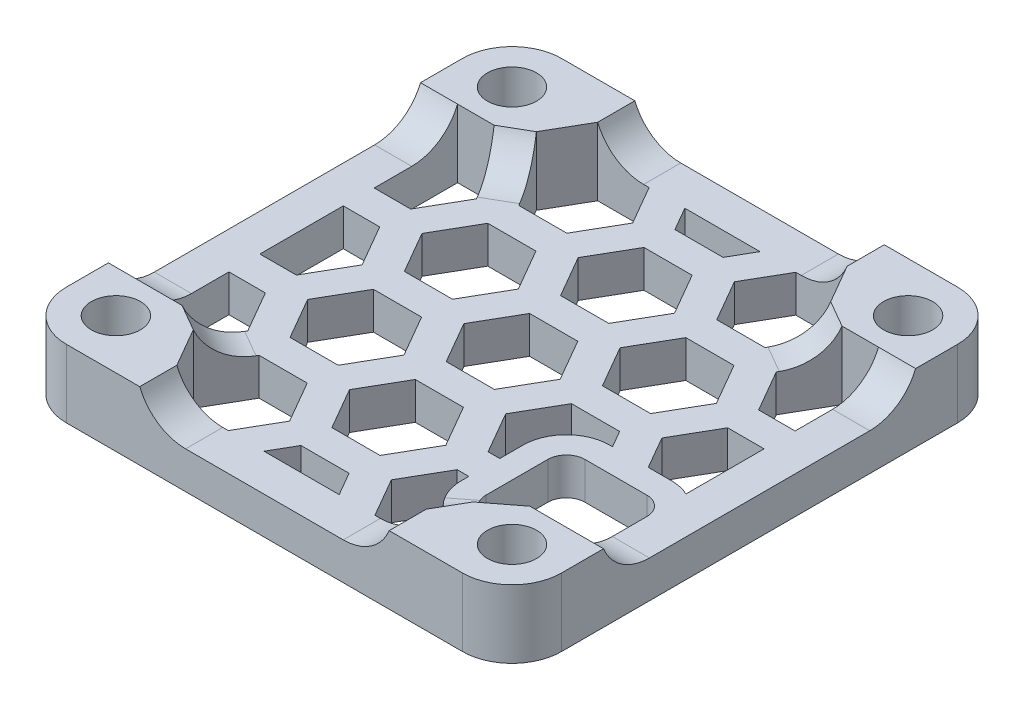
SolidWorks part; units mm, degrees
ref_plane "Front Plane" through (0, 0, 0) normal (0, 0, 1) x (1, 0, 0)
ref_plane "Top Plane" through (0, 0, 0) normal (0, 1, 0) x (1, 0, 0)
ref_plane "Right Plane" through (0, 0, 0) normal (1, 0, 0) x (0, 0, -1)
sketch "Sketch1" plane through (0, 0, 0) normal (0, 1, 0) x (1, 0, 0)
  line L1 (-16, -20) -> (16, -20)
  line L2 (-20, -16) -> (-20, 16)
  line L3 (-16, 20) -> (16, 20)
  line L4 (20, -16) -> (20, 16)
  line L5 (-18.8284, -18.8284) -> (16, 16) construction
  line L6 (-16, 16) -> (18.8284, -18.8284) construction
  circle A0 centre (-16, 16) radius 1.9844
  circle A1 centre (16, 16) radius 1.9844
  circle A2 centre (16, -16) radius 1.9844
  circle A3 centre (-16, -16) radius 1.9844
  arc A4 (-20, 16) -> (-16, 20) centre (-16, 16) cw
  arc A5 (16, 20) -> (20, 16) centre (16, 16) cw
  arc A6 (-16, -20) -> (-20, -16) centre (-16, -16) cw
  arc A7 (16, -20) -> (20, -16) centre (16, -16) ccw
  point P0 (0, 0)
  dimension "D2" = 3.9688
  dimension "D1" = 40
  dimension "D3" = 32
extrude "Boss-Extrude1" add sketch "Sketch1" along normal blind 3 contours L1 A7 L4 A5 L3 A4 L2 A6 A0 A1 A2 A3 | A0 | A1 | A2 | A3 region at (0, 0, 0) region at (-16, 0, -16) region at (16, 0, -16) region at (16, 0, 16) region at (-16, 0, 16)
sketch "Sketch2" plane through (0, 0, 0) normal (0, 1, 0) x (1, 0, 0)
  line L0 (5.0825, -2.9344) -> (2.9175, -1.6844) construction
  line L1 (1.945, -3.3688) -> (3.89, 0)
  line L2 (3.89, 0) -> (1.945, 3.3688)
  line L3 (1.945, 3.3688) -> (-1.945, 3.3688)
  line L4 (-1.945, 3.3688) -> (-3.89, 0)
  line L5 (-3.89, 0) -> (-1.945, -3.3688)
  line L6 (-1.945, -3.3688) -> (1.945, -3.3688)
  line L7 (9.945, -7.9876) -> (11.89, -4.6188)
  line L8 (11.89, -4.6188) -> (9.945, -1.25)
  line L9 (9.945, -1.25) -> (6.055, -1.25)
  line L10 (6.055, -1.25) -> (4.11, -4.6188)
  line L11 (4.11, -4.6188) -> (6.055, -7.9876)
  line L12 (6.055, -7.9876) -> (9.945, -7.9876)
  line L13 (2.9175, 1.6844) -> (5.0825, 2.9344) construction
  line L14 (9.945, 1.25) -> (11.89, 4.6188)
  line L15 (11.89, 4.6188) -> (9.945, 7.9876)
  line L16 (9.945, 7.9876) -> (6.055, 7.9876)
  line L17 (6.055, 7.9876) -> (4.11, 4.6188)
  line L18 (4.11, 4.6188) -> (6.055, 1.25)
  line L19 (6.055, 1.25) -> (9.945, 1.25)
  circle A0 centre (0, 0) radius 3.3688 construction
  circle A1 centre (8, -4.6188) radius 3.3688 construction
  circle A2 centre (8, 4.6188) radius 3.3688 construction
  dimension "D1" = 2.5
  dimension "D2" = 8
  dimension "D3" = 4.6188
sketch "Sketch3" plane through (0, 0, 0) normal (0, 1, 0) x (1, 0, 0)
  line L0 (6.055, -1.25) -> (4.11, -4.6188) construction
  line L1 (4.11, -4.6188) -> (6.055, -7.9876) construction
  line L2 (6.055, -7.9876) -> (9.945, -7.9876) construction
  line L3 (9.945, -7.9876) -> (11.89, -4.6188) construction
  line L4 (11.89, -4.6188) -> (9.945, -1.25) construction
  line L5 (9.945, -1.25) -> (6.055, -1.25) construction
  line L6 (-1.945, 3.3688) -> (-3.89, 0) construction
  line L7 (-3.89, 0) -> (-1.945, -3.3688) construction
  line L8 (-1.945, -3.3688) -> (1.945, -3.3688) construction
  line L9 (1.945, -3.3688) -> (3.89, 0) construction
  line L10 (3.89, 0) -> (1.945, 3.3688) construction
  line L11 (1.945, 3.3688) -> (-1.945, 3.3688) construction
  line L12 (6.055, -1.25) -> (4.11, -4.6188)
  line L13 (4.11, -4.6188) -> (6.055, -7.9876)
  line L14 (6.055, -7.9876) -> (9.945, -7.9876)
  line L15 (9.945, -7.9876) -> (11.89, -4.6188)
  line L16 (11.89, -4.6188) -> (9.945, -1.25)
  line L17 (9.945, -1.25) -> (6.055, -1.25)
  line L18 (-1.945, 3.3688) -> (-3.89, 0)
  line L19 (-3.89, 0) -> (-1.945, -3.3688)
  line L20 (-1.945, -3.3688) -> (1.945, -3.3688)
  line L21 (1.945, -3.3688) -> (3.89, 0)
  line L22 (3.89, 0) -> (1.945, 3.3688)
  line L23 (1.945, 3.3688) -> (-1.945, 3.3688)
  line L24 (14.055, 3.3688) -> (12.11, 0)
  line L25 (12.11, 0) -> (14.055, -3.3688)
  line L26 (14.055, -3.3688) -> (17.945, -3.3688)
  line L27 (17.945, -3.3688) -> (19.89, 0)
  line L28 (19.89, 0) -> (17.945, 3.3688)
  line L29 (17.945, 3.3688) -> (14.055, 3.3688)
  line L30 (22.055, -1.25) -> (20.11, -4.6188)
  line L31 (20.11, -4.6188) -> (22.055, -7.9876)
  line L32 (22.055, -7.9876) -> (25.945, -7.9876)
  line L33 (25.945, -7.9876) -> (27.89, -4.6188)
  line L34 (27.89, -4.6188) -> (25.945, -1.25)
  line L35 (25.945, -1.25) -> (22.055, -1.25)
  line L36 (14.055, 12.6064) -> (12.11, 9.2376)
  line L37 (12.11, 9.2376) -> (14.055, 5.8688)
  line L38 (14.055, 5.8688) -> (17.945, 5.8688)
  line L39 (17.945, 5.8688) -> (19.89, 9.2376)
  line L40 (19.89, 9.2376) -> (17.945, 12.6064)
  line L41 (17.945, 12.6064) -> (14.055, 12.6064)
  line L42 (22.055, 7.9876) -> (20.11, 4.6188)
  line L43 (20.11, 4.6188) -> (22.055, 1.25)
  line L44 (22.055, 1.25) -> (25.945, 1.25)
  line L45 (25.945, 1.25) -> (27.89, 4.6188)
  line L46 (27.89, 4.6188) -> (25.945, 7.9876)
  line L47 (25.945, 7.9876) -> (22.055, 7.9876)
  line L48 (14.055, 21.844) -> (12.11, 18.4752)
  line L49 (12.11, 18.4752) -> (14.055, 15.1064)
  line L50 (14.055, 15.1064) -> (17.945, 15.1064)
  line L51 (17.945, 15.1064) -> (19.89, 18.4752)
  line L52 (19.89, 18.4752) -> (17.945, 21.844)
  line L53 (17.945, 21.844) -> (14.055, 21.844)
  line L54 (22.055, 17.2252) -> (20.11, 13.8564)
  line L55 (20.11, 13.8564) -> (22.055, 10.4876)
  line L56 (22.055, 10.4876) -> (25.945, 10.4876)
  line L57 (25.945, 10.4876) -> (27.89, 13.8564)
  line L58 (27.89, 13.8564) -> (25.945, 17.2252)
  line L59 (25.945, 17.2252) -> (22.055, 17.2252)
  line L60 (-1.945, 12.6064) -> (-3.89, 9.2376)
  line L61 (-3.89, 9.2376) -> (-1.945, 5.8688)
  line L62 (-1.945, 5.8688) -> (1.945, 5.8688)
  line L63 (1.945, 5.8688) -> (3.89, 9.2376)
  line L64 (3.89, 9.2376) -> (1.945, 12.6064)
  line L65 (1.945, 12.6064) -> (-1.945, 12.6064)
  line L66 (6.055, 7.9876) -> (4.11, 4.6188)
  line L67 (4.11, 4.6188) -> (6.055, 1.25)
  line L68 (6.055, 1.25) -> (9.945, 1.25)
  line L69 (9.945, 1.25) -> (11.89, 4.6188)
  line L70 (11.89, 4.6188) -> (9.945, 7.9876)
  line L71 (9.945, 7.9876) -> (6.055, 7.9876)
  line L72 (-1.945, 21.844) -> (-3.89, 18.4752)
  line L73 (-3.89, 18.4752) -> (-1.945, 15.1064)
  line L74 (-1.945, 15.1064) -> (1.945, 15.1064)
  line L75 (1.945, 15.1064) -> (3.89, 18.4752)
  line L76 (3.89, 18.4752) -> (1.945, 21.844)
  line L77 (1.945, 21.844) -> (-1.945, 21.844)
  line L78 (6.055, 17.2252) -> (4.11, 13.8564)
  line L79 (4.11, 13.8564) -> (6.055, 10.4876)
  line L80 (6.055, 10.4876) -> (9.945, 10.4876)
  line L81 (9.945, 10.4876) -> (11.89, 13.8564)
  line L82 (11.89, 13.8564) -> (9.945, 17.2252)
  line L83 (9.945, 17.2252) -> (6.055, 17.2252)
  line L84 (-1.945, 3.3688) -> (14.055, 3.3688) construction
  line L85 (-1.945, 3.3688) -> (-1.945, 12.6064) construction
  line L86 (0, 20) -> (0, -20) construction
  line L87 (-16, 20) -> (16, 20) construction
  line L89 (-9.945, -1.25) -> (-6.055, -1.25)
  line L90 (-11.89, -4.6188) -> (-9.945, -1.25)
  line L91 (-9.945, -7.9876) -> (-11.89, -4.6188)
  line L92 (-6.055, -7.9876) -> (-9.945, -7.9876)
  line L93 (-4.11, -4.6188) -> (-6.055, -7.9876)
  line L94 (-6.055, -1.25) -> (-4.11, -4.6188)
  line L95 (-9.945, 7.9876) -> (-6.055, 7.9876)
  line L96 (-11.89, 4.6188) -> (-9.945, 7.9876)
  line L97 (-9.945, 1.25) -> (-11.89, 4.6188)
  line L98 (-6.055, 1.25) -> (-9.945, 1.25)
  line L99 (-4.11, 4.6188) -> (-6.055, 1.25)
  line L100 (-6.055, 7.9876) -> (-4.11, 4.6188)
  line L101 (-9.945, 17.2252) -> (-6.055, 17.2252)
  line L102 (-11.89, 13.8564) -> (-9.945, 17.2252)
  line L103 (-9.945, 10.4876) -> (-11.89, 13.8564)
  line L104 (-6.055, 10.4876) -> (-9.945, 10.4876)
  line L105 (-4.11, 13.8564) -> (-6.055, 10.4876)
  line L106 (-6.055, 17.2252) -> (-4.11, 13.8564)
  line L107 (-17.945, 12.6064) -> (-14.055, 12.6064)
  line L108 (-19.89, 9.2376) -> (-17.945, 12.6064)
  line L109 (-17.945, 5.8688) -> (-19.89, 9.2376)
  line L110 (-14.055, 5.8688) -> (-17.945, 5.8688)
  line L111 (-12.11, 9.2376) -> (-14.055, 5.8688)
  line L112 (-14.055, 12.6064) -> (-12.11, 9.2376)
  line L113 (-17.945, 3.3688) -> (-14.055, 3.3688)
  line L114 (-19.89, 0) -> (-17.945, 3.3688)
  line L115 (-17.945, -3.3688) -> (-19.89, 0)
  line L116 (-14.055, -3.3688) -> (-17.945, -3.3688)
  line L117 (-12.11, 0) -> (-14.055, -3.3688)
  line L118 (-14.055, 3.3688) -> (-12.11, 0)
  line L119 (-25.945, -1.25) -> (-22.055, -1.25)
  line L120 (-27.89, -4.6188) -> (-25.945, -1.25)
  line L121 (-25.945, -7.9876) -> (-27.89, -4.6188)
  line L122 (-22.055, -7.9876) -> (-25.945, -7.9876)
  line L123 (-20.11, -4.6188) -> (-22.055, -7.9876)
  line L124 (-22.055, -1.25) -> (-20.11, -4.6188)
  line L125 (-25.945, 7.9876) -> (-22.055, 7.9876)
  line L126 (-27.89, 4.6188) -> (-25.945, 7.9876)
  line L127 (-25.945, 1.25) -> (-27.89, 4.6188)
  line L128 (-22.055, 1.25) -> (-25.945, 1.25)
  line L129 (-20.11, 4.6188) -> (-22.055, 1.25)
  line L130 (-22.055, 7.9876) -> (-20.11, 4.6188)
  line L131 (-25.945, 17.2252) -> (-22.055, 17.2252)
  line L132 (-27.89, 13.8564) -> (-25.945, 17.2252)
  line L133 (-25.945, 10.4876) -> (-27.89, 13.8564)
  line L134 (-22.055, 10.4876) -> (-25.945, 10.4876)
  line L135 (-20.11, 13.8564) -> (-22.055, 10.4876)
  line L136 (-22.055, 17.2252) -> (-20.11, 13.8564)
  line L137 (-17.945, 21.844) -> (-14.055, 21.844)
  line L138 (-19.89, 18.4752) -> (-17.945, 21.844)
  line L139 (-17.945, 15.1064) -> (-19.89, 18.4752)
  line L140 (-14.055, 15.1064) -> (-17.945, 15.1064)
  line L141 (-12.11, 18.4752) -> (-14.055, 15.1064)
  line L142 (-14.055, 21.844) -> (-12.11, 18.4752)
  line L143 (0, 0) -> (20, 0) construction
  line L145 (17.945, -21.844) -> (14.055, -21.844)
  line L146 (19.89, -18.4752) -> (17.945, -21.844)
  line L147 (17.945, -15.1064) -> (19.89, -18.4752)
  line L148 (14.055, -15.1064) -> (17.945, -15.1064)
  line L149 (12.11, -18.4752) -> (14.055, -15.1064)
  line L150 (14.055, -21.844) -> (12.11, -18.4752)
  line L151 (25.945, -17.2252) -> (22.055, -17.2252)
  line L152 (27.89, -13.8564) -> (25.945, -17.2252)
  line L153 (25.945, -10.4876) -> (27.89, -13.8564)
  line L154 (22.055, -10.4876) -> (25.945, -10.4876)
  line L155 (20.11, -13.8564) -> (22.055, -10.4876)
  line L156 (22.055, -17.2252) -> (20.11, -13.8564)
  line L157 (17.945, -12.6064) -> (14.055, -12.6064)
  line L158 (19.89, -9.2376) -> (17.945, -12.6064)
  line L159 (17.945, -5.8688) -> (19.89, -9.2376)
  line L160 (14.055, -5.8688) -> (17.945, -5.8688)
  line L161 (12.11, -9.2376) -> (14.055, -5.8688)
  line L162 (14.055, -12.6064) -> (12.11, -9.2376)
  line L163 (9.945, -17.2252) -> (6.055, -17.2252)
  line L164 (11.89, -13.8564) -> (9.945, -17.2252)
  line L165 (9.945, -10.4876) -> (11.89, -13.8564)
  line L166 (6.055, -10.4876) -> (9.945, -10.4876)
  line L167 (4.11, -13.8564) -> (6.055, -10.4876)
  line L168 (6.055, -17.2252) -> (4.11, -13.8564)
  line L169 (1.945, -21.844) -> (-1.945, -21.844)
  line L170 (3.89, -18.4752) -> (1.945, -21.844)
  line L171 (1.945, -15.1064) -> (3.89, -18.4752)
  line L172 (-1.945, -15.1064) -> (1.945, -15.1064)
  line L173 (-3.89, -18.4752) -> (-1.945, -15.1064)
  line L174 (-1.945, -21.844) -> (-3.89, -18.4752)
  line L175 (1.945, -12.6064) -> (-1.945, -12.6064)
  line L176 (3.89, -9.2376) -> (1.945, -12.6064)
  line L177 (1.945, -5.8688) -> (3.89, -9.2376)
  line L178 (-1.945, -5.8688) -> (1.945, -5.8688)
  line L179 (-3.89, -9.2376) -> (-1.945, -5.8688)
  line L180 (-1.945, -12.6064) -> (-3.89, -9.2376)
  line L181 (-11.89, -13.8564) -> (-9.945, -17.2252)
  line L182 (-9.945, -10.4876) -> (-11.89, -13.8564)
  line L183 (-6.055, -10.4876) -> (-9.945, -10.4876)
  line L184 (-4.11, -13.8564) -> (-6.055, -10.4876)
  line L185 (-6.055, -17.2252) -> (-4.11, -13.8564)
  line L186 (-9.945, -17.2252) -> (-6.055, -17.2252)
  line L187 (-19.89, -18.4752) -> (-17.945, -21.844)
  line L188 (-17.945, -15.1064) -> (-19.89, -18.4752)
  line L189 (-14.055, -15.1064) -> (-17.945, -15.1064)
  line L190 (-12.11, -18.4752) -> (-14.055, -15.1064)
  line L191 (-14.055, -21.844) -> (-12.11, -18.4752)
  line L192 (-17.945, -21.844) -> (-14.055, -21.844)
  line L193 (-27.89, -13.8564) -> (-25.945, -17.2252)
  line L194 (-25.945, -10.4876) -> (-27.89, -13.8564)
  line L195 (-22.055, -10.4876) -> (-25.945, -10.4876)
  line L196 (-20.11, -13.8564) -> (-22.055, -10.4876)
  line L197 (-22.055, -17.2252) -> (-20.11, -13.8564)
  line L198 (-25.945, -17.2252) -> (-22.055, -17.2252)
  line L199 (-19.89, -9.2376) -> (-17.945, -12.6064)
  line L200 (-17.945, -5.8688) -> (-19.89, -9.2376)
  line L201 (-14.055, -5.8688) -> (-17.945, -5.8688)
  line L202 (-12.11, -9.2376) -> (-14.055, -5.8688)
  line L203 (-14.055, -12.6064) -> (-12.11, -9.2376)
  line L204 (-17.945, -12.6064) -> (-14.055, -12.6064)
  line L205 (20, -16) -> (20, 16) construction
  line L207 (-16, -20) -> (16, -20) construction
  dimension "D3" = 16
  dimension "D4" = 9.2376
  dimension "D1" = 2
  dimension "D2" = 3
extrude "Cut-Extrude1" cut sketch "Sketch3" along normal through all
sketch "Sketch4" plane through (0, 0, 0) normal (0, 1, 0) x (1, 0, 0)
  line L0 (12.9617, 17) -> (-12.9617, 17)
  line L1 (-17, 15.1064) -> (-17, -15.1064)
  line L2 (-12.9617, -17) -> (12.9617, -17)
  line L3 (17, -15.1064) -> (17, 15.1064)
  line L4 (-20, 16) -> (-20, -16)
  line L5 (16, 20) -> (-16, 20)
  line L6 (20, -16) -> (20, 16)
  line L7 (-16, -20) -> (16, -20)
  line L8 (-20, 16) -> (-20, -16)
  line L9 (16, 20) -> (-16, 20)
  line L10 (20, -16) -> (20, 16)
  line L11 (-16, -20) -> (16, -20)
  line L12 (-14.055, -15.1064) -> (-17.945, -15.1064) construction
  line L13 (-12.11, -18.4752) -> (-14.055, -15.1064) construction
  line L14 (14.055, -15.1064) -> (12.11, -18.4752) construction
  line L15 (17.945, -15.1064) -> (14.055, -15.1064) construction
  line L16 (12.11, 18.4752) -> (14.055, 15.1064) construction
  line L17 (14.055, 15.1064) -> (17.945, 15.1064) construction
  line L18 (-17.945, 15.1064) -> (-14.055, 15.1064) construction
  line L19 (-14.055, 15.1064) -> (-12.11, 18.4752) construction
  line L20 (-14.055, -15.1064) -> (-17, -15.1064)
  line L21 (-12.9617, -17) -> (-14.055, -15.1064)
  line L22 (14.055, -15.1064) -> (12.9617, -17)
  line L23 (17, -15.1064) -> (14.055, -15.1064)
  line L24 (12.9617, 17) -> (14.055, 15.1064)
  line L25 (14.055, 15.1064) -> (17, 15.1064)
  line L26 (-17, 15.1064) -> (-14.055, 15.1064)
  line L27 (-14.055, 15.1064) -> (-12.9617, 17)
  line L28 (16, 17) -> (-16, 17) construction
  line L29 (-17, 16) -> (-17, -16) construction
  line L30 (17, -16) -> (17, 16) construction
  line L31 (-16, -17) -> (16, -17) construction
  arc A12 (-16, 20) -> (-20, 16) centre (-16, 16) ccw
  arc A13 (20, 16) -> (16, 20) centre (16, 16) ccw
  arc A14 (16, -20) -> (20, -16) centre (16, -16) ccw
  arc A15 (-20, -16) -> (-16, -20) centre (-16, -16) ccw
  arc A16 (-16, 20) -> (-20, 16) centre (-16, 16) ccw
  arc A17 (20, 16) -> (16, 20) centre (16, 16) ccw
  arc A18 (16, -20) -> (20, -16) centre (16, -16) ccw
  arc A19 (-20, -16) -> (-16, -20) centre (-16, -16) ccw
  arc A20 (-16, 17) -> (-17, 16) centre (-16, 16) ccw construction
  arc A21 (17, 16) -> (16, 17) centre (16, 16) ccw construction
  arc A22 (-17, -16) -> (-16, -17) centre (-16, -16) ccw construction
  arc A23 (16, -17) -> (17, -16) centre (16, -16) ccw construction
  dimension "D5" = 0
  dimension "D6" = 3
extrude "Boss-Extrude2" add sketch "Sketch4" along normal up to surface (3 mm away) up to face at (8, 3, 4.6188)
sketch "Sketch6" plane through (0, 3, 0) normal (0, 1, 0) x (1, 0, 0)
  line L0 (-20, 12.6064) -> (-14.055, 12.6064)
  line L1 (-20, -16) -> (-20, 16) construction
  line L3 (-16, 20) -> (16, 20) construction
  line L4 (-20, 12.6064) -> (-20, 16)
  line L5 (-16, 20) -> (-10.075, 20)
  line L6 (-14.055, 12.6064) -> (-11.89, 13.8564)
  line L9 (14.055, 12.6064) -> (11.89, 13.8564)
  line L10 (-14.055, 12.6064) -> (-11.89, 13.8564) construction
  line L11 (-10.075, 17) -> (-11.89, 13.8564) construction
  line L12 (-10.075, 17) -> (-10.075, 20)
  line L13 (-11.89, 13.8564) -> (-10.075, 17)
  line L14 (0, 0) -> (0, 20) construction
  line L15 (0, 0) -> (20, 0) construction
  line L16 (20, -16) -> (20, 16) construction
  line L17 (20, 12.6064) -> (14.055, 12.6064)
  line L18 (20, 12.6064) -> (20, 16)
  line L19 (16, 20) -> (10.075, 20)
  line L20 (10.075, 17) -> (10.075, 20)
  line L21 (11.89, 13.8564) -> (10.075, 17)
  line L22 (16, -20) -> (10.075, -20)
  line L23 (10.075, -17) -> (10.075, -20)
  line L24 (11.89, -13.8564) -> (10.075, -17)
  line L25 (14.055, -12.6064) -> (11.89, -13.8564)
  line L26 (20, -12.6064) -> (14.055, -12.6064)
  line L27 (20, -12.6064) -> (20, -16)
  line L28 (-14.055, -12.6064) -> (-11.89, -13.8564)
  line L29 (-20, -12.6064) -> (-14.055, -12.6064)
  line L30 (-20, -12.6064) -> (-20, -16)
  line L31 (-16, -20) -> (-10.075, -20)
  line L32 (-10.075, -17) -> (-10.075, -20)
  line L33 (-11.89, -13.8564) -> (-10.075, -17)
  arc A1 (16, 20) -> (20, 16) centre (16, 16) cw
  arc A2 (-16, 20) -> (-20, 16) centre (-16, 16) ccw construction
  arc A3 (-16, 20) -> (-20, 16) centre (-16, 16) ccw
  arc A4 (16, -20) -> (20, -16) centre (16, -16) ccw
  arc A5 (-16, -20) -> (-20, -16) centre (-16, -16) cw
extrude "Boss-Extrude5" add sketch "Sketch6" along normal blind 2.5 contours L5 A3 L4 L0 L6 L13 L12 | A1 L19 L20 L21 L9 L17 L18 | A5 L31 L32 L33 L28 L29 L30 | L22 A4 L27 L26 L25 L24 L23 region at (-15.2099, 3, -16.3941) region at (15.2099, 3, -16.3941) region at (15.2099, 3, 16.3941) region at (-15.2099, 3, 16.3941)
fillet "Fillet1" radius 4 10 edges at (18.5, 3, -12.6064) (12.9725, 3, -13.2314) (10.075, 3, -18.5) (10.075, 3, 18.5) (-10.075, 3, 18.5) (-12.9725, 3, 13.2314) (-18.5, 3, 12.6064) (-10.075, 3, -18.5) (-12.9725, 3, -13.2314) (-18.5, 3, -12.6064)
sketch "Sketch7" plane through (0, 3, 0) normal (0, 1, 0) x (1, 0, 0)
  line L0 (11.89, -4.6188) -> (14.055, -5.8688)
  line L1 (14.055, -5.8688) -> (12.11, -9.2376)
  line L2 (12.11, -9.2376) -> (9.945, -7.9876)
  line L3 (9.945, -7.9876) -> (11.89, -4.6188)
  line L5 (10.5, -4.6064) -> (15.5, -4.6064)
  line L6 (9, -6.1064) -> (9, -11.1064)
  line L7 (10.5, -12.6064) -> (15.5, -12.6064)
  line L8 (17, -6.1064) -> (17, -11.1064)
  line L9 (17, -12.6064) -> (17, -5.8688) construction
  line L10 (20, -12.6064) -> (14.055, -12.6064) construction
  line L11 (7, -6.1064) -> (7, -11.1064)
  line L12 (10.5, -14.6064) -> (15.5, -14.6064)
  line L13 (19, -6.1064) -> (19, -11.1064)
  line L14 (10.5, -2.6064) -> (15.5, -2.6064)
  arc A0 (9, -11.1064) -> (10.5, -12.6064) centre (10.5, -11.1064) ccw
  arc A1 (17, -11.1064) -> (15.5, -12.6064) centre (15.5, -11.1064) cw
  arc A2 (15.5, -4.6064) -> (17, -6.1064) centre (15.5, -6.1064) cw
  arc A3 (10.5, -4.6064) -> (9, -6.1064) centre (10.5, -6.1064) ccw
  arc A4 (10.5, -2.6064) -> (7, -6.1064) centre (10.5, -6.1064) ccw
  arc A5 (7, -11.1064) -> (10.5, -14.6064) centre (10.5, -11.1064) ccw
  arc A6 (19, -11.1064) -> (15.5, -14.6064) centre (15.5, -11.1064) cw
  arc A7 (15.5, -2.6064) -> (19, -6.1064) centre (15.5, -6.1064) cw
  point P12 (0, 0)
  point P13 (15.2449, -3.7054)
  point P15 (9.945, -2.9344)
  point P23 (17, -12.6064)
  point P26 (17, -4.6064)
  point P29 (9, -4.6064)
  dimension "D3" = 1.5
  dimension "D1" = 8
  dimension "D2" = 8
  dimension "D4" = 2
extrude "Boss-Extrude6" add sketch "Sketch7" against normal through all contours A7 L14 A4 L11 A5 L12 A6 L13 A3 L5 A2 L8 A1 L7 A0 L6 region at (8.1451, 3, 3.7515)
extrude "Cut-Extrude5" cut sketch "Sketch7<3>" against normal through all both and the other way through all contours L5 A3 L6 A0 L7 A1 L8 A2 L2 L3 L0 L1 | L3 L2 L1 L0 region at (12, 3, 6.9282) region at (13.1858, 3, 8.9182)
sketch "Sketch7<3>" plane through (0, 3, 0) normal (0, 1, 0) x (1, 0, 0) same geometry as "Sketch7"
extrude "Cut-Extrude2" cut sketch "Sketch1<3>" along normal through all contours A1 | A3 | A2 | A0 region at (16, 0, -16) region at (16, 0, 16) region at (-16, 0, 16)
sketch "Sketch1<3>" plane through (0, 0, 0) normal (0, 1, 0) x (1, 0, 0) same geometry as "Sketch1"
sketch "Sketch8" plane through (0, 3, 0) normal (0, 1, 0) x (1, 0, 0)
  line L0 (11.4569, -14.6064) -> (14.055, -12.6064)
  line L1 (14.055, -12.6064) -> (11.89, -13.8564)
  line L2 (11.89, -13.8564) -> (11.4569, -14.6064)
extrude "Cut-Extrude6" cut sketch "Sketch8" along normal up to next
fillet "Fillet4" radius 4 2 edges at (17.75, 3, 12.6064) (12.756, 3, 13.6064)
